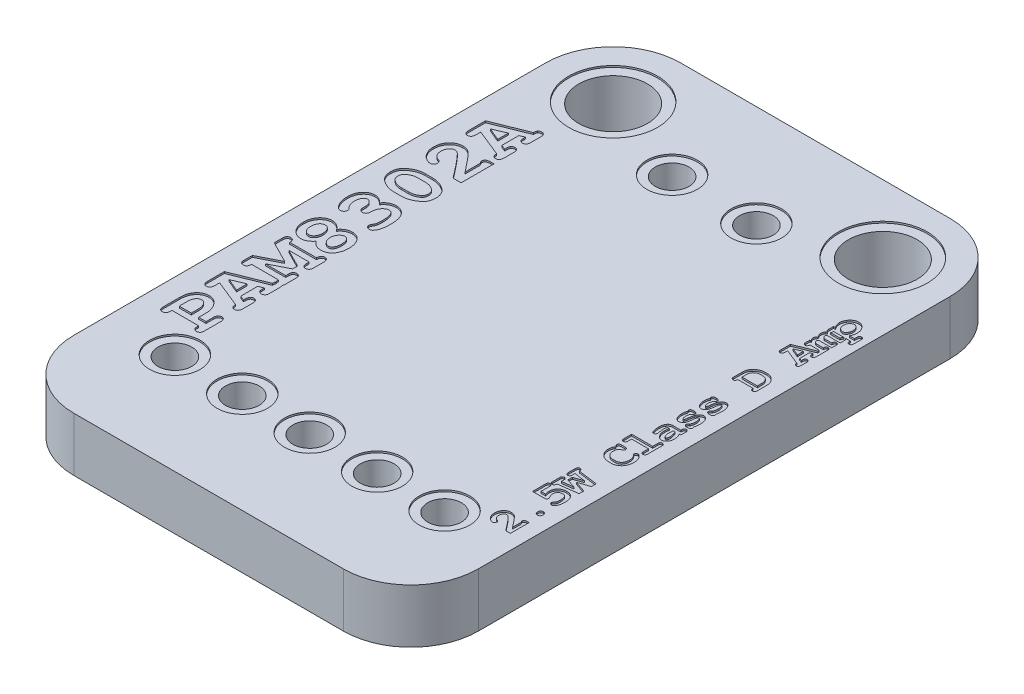
SolidWorks part; units mm, degrees
ref_plane "Front Plane" through (0, 0, 0) normal (0, 0, 1) x (1, 0, 0)
ref_plane "Top Plane" through (0, 0, 0) normal (0, 1, 0) x (1, 0, 0)
ref_plane "Right Plane" through (0, 0, 0) normal (1, 0, 0) x (0, 0, -1)
sketch "Sketch1" plane through (0, 0, 0) normal (0, 1, 0) x (1, 0, 0)
  line L0 (-1.5875, 7.62) -> (1.5875, 7.62) construction
  line L1 (-5.08, -11.43) -> (5.08, -11.43)
  line L2 (-7.62, -8.89) -> (-7.62, 8.89)
  line L3 (-5.08, 11.43) -> (5.08, 11.43)
  line L4 (7.62, -8.89) -> (7.62, 8.89)
  line L5 (-5.08, -7.62) -> (-2.54, -7.62) construction
  line L6 (-2.54, -7.62) -> (0, -7.62) construction
  line L7 (0, -7.62) -> (2.54, -7.62) construction
  line L8 (-5.08, -11.43) -> (5.08, -11.43)
  line L9 (7.62, -8.89) -> (7.62, 8.89)
  line L10 (5.08, 11.43) -> (-5.08, 11.43)
  line L11 (-7.62, 8.89) -> (-7.62, -8.89)
  line L12 (2.54, -7.62) -> (5.08, -7.62) construction
  arc A0 (-5.08, -11.43) -> (-7.62, -8.89) centre (-5.08, -8.89) cw
  arc A1 (5.08, -11.43) -> (7.62, -8.89) centre (5.08, -8.89) ccw
  arc A2 (5.08, 11.43) -> (7.62, 8.89) centre (5.08, 8.89) cw
  arc A3 (-7.62, 8.89) -> (-5.08, 11.43) centre (-5.08, 8.89) cw
  circle A4 centre (-5.08, 8.89) radius 1.294
  circle A5 centre (5.08, 8.89) radius 1.294
  circle A6 centre (-5.08, 8.89) radius 1.675
  circle A7 centre (5.08, 8.89) radius 1.675
  arc A8 (-7.62, -8.89) -> (-5.08, -11.43) centre (-5.08, -8.89) ccw
  arc A9 (5.08, -11.43) -> (7.62, -8.89) centre (5.08, -8.89) ccw
  arc A10 (7.62, 8.89) -> (5.08, 11.43) centre (5.08, 8.89) ccw
  arc A11 (-5.08, 11.43) -> (-7.62, 8.89) centre (-5.08, 8.89) ccw
  circle A12 centre (-1.5875, 7.62) radius 0.9525
  circle A13 centre (1.5875, 7.62) radius 0.9525
  circle A14 centre (-1.5875, 7.62) radius 0.635
  circle A15 centre (1.5875, 7.62) radius 0.635
  circle A16 centre (0, -7.62) radius 0.9525
  circle A17 centre (-5.08, -7.62) radius 0.9525
  circle A18 centre (5.08, -7.62) radius 0.9525
  circle A19 centre (2.54, -7.62) radius 0.9525
  circle A20 centre (-2.54, -7.62) radius 0.9525
  circle A21 centre (-5.08, -7.62) radius 0.635
  circle A22 centre (-2.54, -7.62) radius 0.635
  circle A23 centre (0, -7.62) radius 0.635
  circle A24 centre (2.54, -7.62) radius 0.635
  circle A25 centre (5.08, -7.62) radius 0.635
  point P4 (-7.62, 0)
  point P6 (0, -11.43)
  point P9 (-7.62, -11.43)
  point P14 (7.62, 11.43)
  point P17 (-7.62, 11.43)
  point P32 (0, 7.62)
  point P33 (0, 11.43)
  point P43 (0, -8.0121)
  point P56 (0, -11.43)
  point P61 (-7.62, 0)
  dimension "D3" = 2.54
  dimension "D4" = 3.35
  dimension "D7" = 1.905
  dimension "D8" = 1.27
  dimension "D13" = 2.54
  dimension "D5" = 0.381
  dimension "D1" = 15.24
  dimension "D2" = 22.86
  dimension "D6" = 3.175
  dimension "D9" = 3.81
  dimension "D10" = 3.81
  dimension "D11" = 22.86
  dimension "D12" = 15.24
extrude "Boss-Extrude1" add sketch "Sketch1" along normal mid plane 2.032 contours A3 L2 A0 L1 A1 L4 A2 L3 A20 A19 A18 A17 A16 A13 A12 A7 A6 region at (0, 0, 0.2999)
extrude "Boss-Extrude2" add sketch "Sketch1<3>" along normal mid plane 1.905 contours A6 A4 | A12 A14 | A13 A15 | A7 A5 | A17 A21 | A20 A22 | A16 A23 | A19 A24 | A18 A25 region at (-6.7076, 0, -8.89) region at (3.4524, 0, -8.89) region at (-2.5131, 0, -7.62) region at (0.6619, 0, -7.62) region at (-0.9256, 0, 7.62) region at (-6.0056, 0, 7.62) region at (4.1544, 0, 7.62) region at (1.6144, 0, 7.62) region at (-3.4656, 0, 7.62)
sketch "Sketch1<3>" plane through (0, 0, 0) normal (0, 1, 0) x (1, 0, 0) same geometry as "Sketch1"
sketch "Sketch3" plane through (0, 1.016, 0) normal (0, 1, 0) x (1, 0, 0)
  line L0 (-5.2993, -11.43) -> (-5.2993, 11.43) construction
  line L1 (-5.08, 11.43) -> (5.08, 11.43) construction
  line L2 (-5.08, -11.43) -> (5.08, -11.43) construction
  line L3 (7.0658, 11.43) -> (7.0658, -11.43) construction
  text T0 "PAM8302A   " font "Courier New" height in points 7
  text T1 "     2.5W Class D Amp" font "Courier New" height in points 4
extrude "Cut-Extrude1" cut sketch "Sketch3" against normal mid plane 0.127
